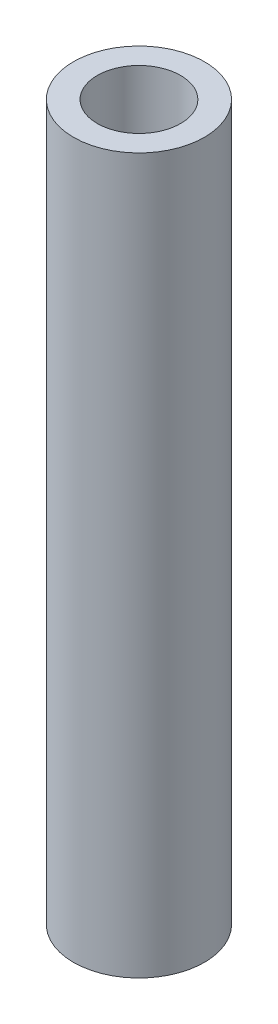
SolidWorks part; units mm, degrees
ref_plane "Front Plane" through (0, 0, 0) normal (0, 0, 1) x (1, 0, 0)
ref_plane "Top Plane" through (0, 0, 0) normal (0, 1, 0) x (1, 0, 0)
ref_plane "Right Plane" through (0, 0, 0) normal (1, 0, 0) x (0, 0, -1)
sketch "Sketch1" plane through (0, 0, 0) normal (0, 1, 0) x (1, 0, 0)
  circle A0 centre (0, 0) radius 1.75
  circle A1 centre (0, 0) radius 2.75
  dimension "D1" = 3.5
  dimension "D2" = 5.5
extrude "Boss-Extrude1" add sketch "Sketch1" along normal blind 30
ref_axis "Axis1" through (0, 30, 0) along (0, -1, 0)
